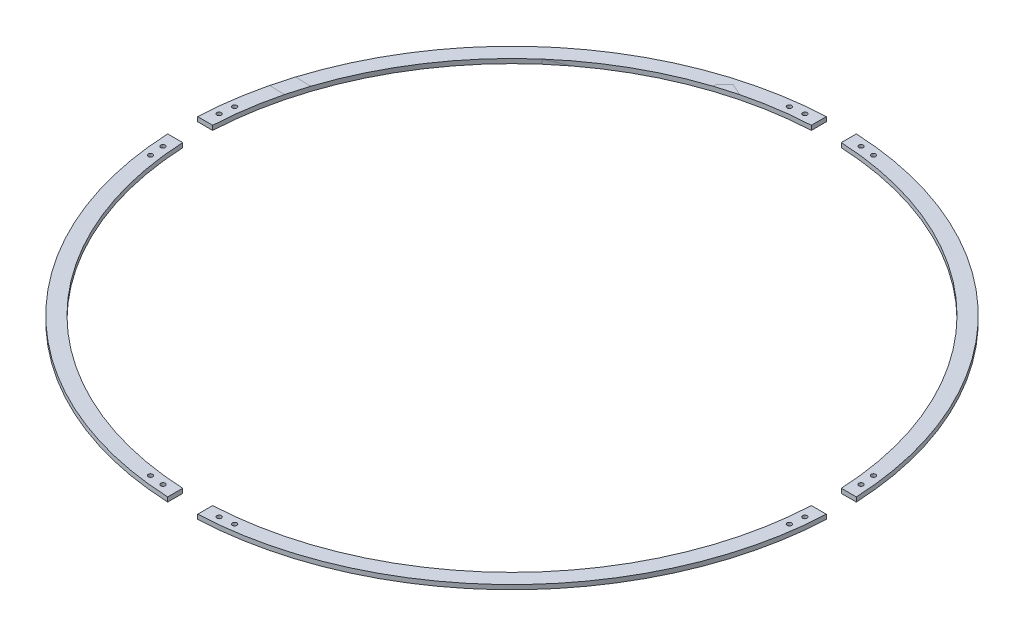
SolidWorks part; units mm, degrees
ref_plane "Front Plane" through (0, 0, 0) normal (0, 0, 1) x (1, 0, 0)
ref_plane "Top Plane" through (0, 0, 0) normal (0, 1, 0) x (1, 0, 0)
ref_plane "Right Plane" through (0, 0, 0) normal (1, 0, 0) x (0, 0, -1)
sketch "Sketch5" plane through (0, 0, 0) normal (0, 1, 0) x (1, 0, 0)
  line L0 (-220, 0) -> (220, 0) construction
  line L1 (0, 220) -> (0, -220) construction
  line L2 (-10, 219.7726) -> (-10, 0) construction
  line L3 (0, 10) -> (-219.7726, 10) construction
  line L4 (-10, 219.7726) -> (-10, 209.7618)
  line L5 (-219.7726, 10) -> (-209.7618, 10)
  arc A0 (-10, 219.7726) -> (-219.7726, 10) centre (0, 0) ccw
  arc A1 (-10, 209.7618) -> (-209.7618, 10) centre (0, 0) ccw
  circle A2 centre (0, 0) radius 215 construction
  arc A3 (-10, 219.7726) -> (-219.7726, 10) centre (0, 0) ccw construction
  arc A4 (-10, 209.7618) -> (-209.7618, 10) centre (0, 0) ccw construction
  arc A5 (-210, 0) -> (0, 210) centre (0, 0) ccw construction
  arc A6 (-220, 0) -> (0, 220) centre (0, 0) ccw construction
  dimension "D1" = 220
  dimension "D3" = 210
  dimension "D2" = 5
  dimension "D4" = 10
  dimension "D5" = 10
extrude "Boss-Extrude2" add sketch "Sketch5" along normal mid plane 3
ref_axis "Axis1" through (-132.6096, 0, 0) along (1, 0, 0)
ref_plane "Plane1" through (0, 7.5, 0) normal (0, 1, 0) x (1, 0, 0)
sketch "Sketch6" plane through (0, 1.5, 0) normal (0, 1, 0) x (1, 0, 0)
  line L0 (0, 0) -> (-214.1819, 18.7385) construction
  line L1 (0, 0) -> (-213.1606, 28.0631) construction
  line L3 (-215, 0) -> (215, 0) construction
  line L4 (0, 215) -> (0, -215) construction
  line L5 (0, 0) -> (-18.7385, 214.1819) construction
  line L6 (0, 0) -> (-28.0631, 213.1606) construction
  circle A0 centre (0, 0) radius 215 construction
  circle A1 centre (0, 0) radius 215 construction
  dimension "D1" = 5
  dimension "D2" = 7.5
  dimension "D3" = 5
  dimension "D4" = 7.5
hole_wizard "Ø3.0 (3) Diameter Hole1" positions "Sketch9" profile "Sketch10" hole size "Ø3.0" standard "ISO" end condition through all
sketch "Sketch9" plane through (0, 1.5, 0) normal (0, 1, 0) x (1, 0, 0)
  point P0 (-214.1819, 18.7385)
  point P3 (-213.1606, 28.0631)
  point P6 (-28.0631, 213.1606)
  point P9 (-18.7385, 214.1819)
sketch "Sketch10" plane through (-214.1819, 1.5, -18.7385) normal (1, 0, 0) x (0, 0, 1)
  line L0 (0, 0) -> (0, 3)
  line L1 (0, 3) -> (1.5, 3)
  line L2 (1.5, 3) -> (1.5, 0)
  line L5 (1.5, 0) -> (0, 0)
  line L11 (0, -6.35) -> (0, 107.95) construction
  dimension "Thru Hole Dia." = 3
  dimension "Thru Hole Depth" = 3
sketch "Sketch1" plane through (0, 0, 0) normal (0, 1, 0) x (1, 0, 0)
  circle A0 centre (0, 0) radius 210
  circle A1 centre (0, 0) radius 220
  dimension "D1" = 420
  dimension "D2" = 440
extrude "Boss-Extrude1" add sketch "Sketch1" along normal mid plane 3
sketch "pitch" plane through (0, 0, 0) normal (0, 1, 0) x (1, 0, 0)
  line L0 (-215, 0) -> (215, 0) construction
  dimension "D1" = 430
sketch "circle" plane through (0, 0, 0) normal (0, 1, 0) x (1, 0, 0)
  circle A0 centre (0, 0) radius 215 construction
sketch "Sketch2" plane through (0, 0, 0) normal (0, 1, 0) x (1, 0, 0)
  line L0 (-215, 0) -> (215, 0) construction
  line L1 (10, 220) -> (-10, 220)
  line L2 (10, 220) -> (10, -220)
  line L3 (10, -220) -> (-10, -220)
  line L4 (-10, 220) -> (-10, -220)
  line L5 (10, 220) -> (-10, -220) construction
  line L6 (10, -220) -> (-10, 220) construction
  line L8 (220, 10) -> (-220, 10)
  line L9 (220, 10) -> (220, -10)
  line L10 (220, -10) -> (-220, -10)
  line L11 (-220, 10) -> (-220, -10)
  line L12 (220, 10) -> (-220, -10) construction
  line L13 (220, -10) -> (-220, 10) construction
  circle A0 centre (0, 0) radius 220 construction
  point P0 (0, 0)
  point P10 (0, 0)
  dimension "D1" = 20
  dimension "D2" = 20
extrude "quadruple" cut sketch "Sketch2" against normal through all both and the other way through all contours L8 L11 L10 L9 | L4 L3 L2 L1
sketch "Sketch3" plane through (0, 0, 0) normal (0, 1, 0) x (1, 0, 0)
  line L0 (0, 220) -> (0, -220) construction
  circle A0 centre (0, 0) radius 220 construction
  circle A1 centre (0, 0) radius 220
sketch "Sketch4" plane through (0, 0, 0) normal (0, 1, 0) x (1, 0, 0)
  circle A0 centre (213.1606, 28.0631) radius 1.5 construction
  circle A1 centre (214.1819, 18.7385) radius 1.5 construction
  circle A2 centre (214.1819, -18.7385) radius 1.5 construction
  circle A3 centre (213.1606, -28.0631) radius 1.5 construction
  circle A4 centre (213.1606, 28.0631) radius 1.5
  circle A5 centre (214.1819, 18.7385) radius 1.5
  circle A6 centre (214.1819, -18.7385) radius 1.5
  circle A7 centre (213.1606, -28.0631) radius 1.5
  circle A8 centre (-28.0631, 213.1606) radius 1.5 construction
  circle A9 centre (-18.7385, 214.1819) radius 1.5 construction
  circle A10 centre (28.0631, 213.1606) radius 1.5 construction
  circle A11 centre (18.7385, 214.1819) radius 1.5 construction
  circle A12 centre (-28.0631, 213.1606) radius 1.5
  circle A13 centre (-18.7385, 214.1819) radius 1.5
  circle A14 centre (28.0631, 213.1606) radius 1.5
  circle A15 centre (18.7385, 214.1819) radius 1.5
  circle A16 centre (-213.1606, 28.0631) radius 1.5 construction
  circle A17 centre (-214.1819, 18.7385) radius 1.5 construction
  circle A18 centre (-214.1819, -18.7385) radius 1.5 construction
  circle A19 centre (-213.1606, -28.0631) radius 1.5 construction
  circle A20 centre (-213.1606, 28.0631) radius 1.5
  circle A21 centre (-214.1819, 18.7385) radius 1.5
  circle A22 centre (-214.1819, -18.7385) radius 1.5
  circle A23 centre (-213.1606, -28.0631) radius 1.5
  circle A24 centre (-28.0631, -213.1606) radius 1.5 construction
  circle A25 centre (-18.7385, -214.1819) radius 1.5 construction
  circle A26 centre (18.7385, -214.1819) radius 1.5 construction
  circle A27 centre (28.0631, -213.1606) radius 1.5 construction
  circle A28 centre (-28.0631, -213.1606) radius 1.5
  circle A29 centre (-18.7385, -214.1819) radius 1.5
  circle A30 centre (18.7385, -214.1819) radius 1.5
  circle A31 centre (28.0631, -213.1606) radius 1.5
extrude "Cut-Extrude1" cut sketch "Sketch4" against normal through all both and the other way through all
